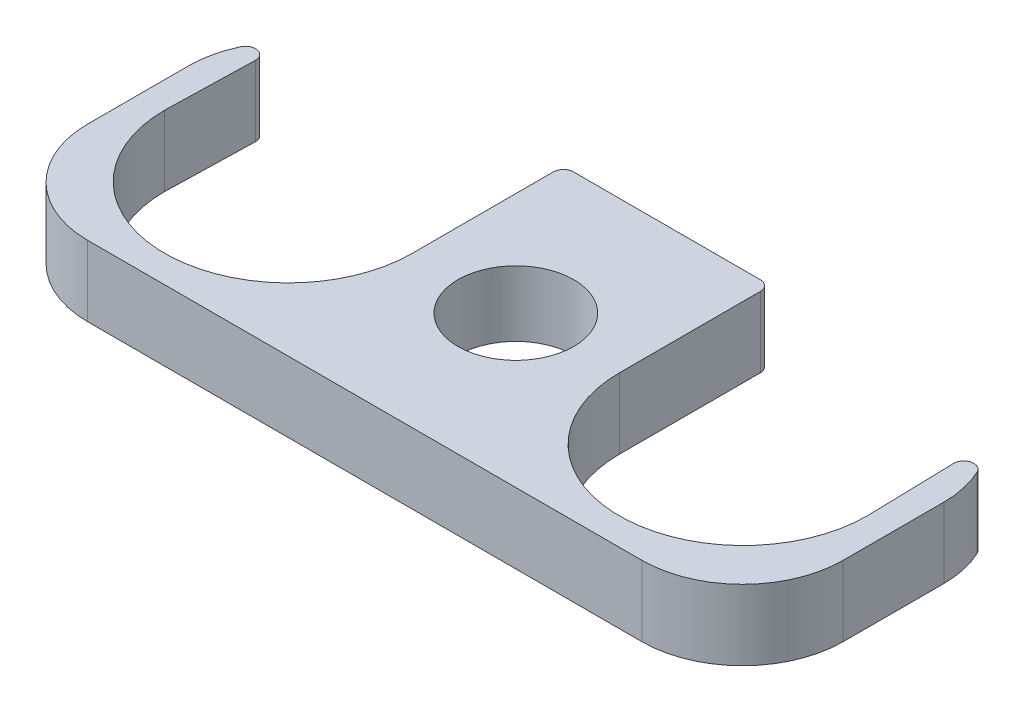
SolidWorks part; units mm, degrees
material "PLA"
ref_plane "Front Plane" through (0, 0, 0) normal (0, 0, 1) x (1, 0, 0)
ref_plane "Top Plane" through (0, 0, 0) normal (0, 1, 0) x (1, 0, 0)
ref_plane "Right Plane" through (0, 0, 0) normal (1, 0, 0) x (0, 0, -1)
sketch "Sketch1" plane through (0, 0, 0) normal (0, 1, 0) x (1, 0, 0)
  line L0 (0, 15) -> (0, -15) construction
  line L1 (-27.5, -15) -> (27.5, -15)
  line L2 (-37.5, -5) -> (-37.5, 5)
  line L3 (-27.5, 15) -> (27.5, 15)
  line L4 (37.5, -5) -> (37.5, 5)
  line L7 (-37.5, 15) -> (0, 15) construction
  line L8 (0, 15) -> (-18.75, 15) construction
  circle A0 centre (0, 0) radius 5.75
  arc A2 (27.5, 15) -> (37.5, 5) centre (27.5, 5) cw
  arc A3 (27.5, -15) -> (37.5, -5) centre (27.5, -5) ccw
  arc A4 (-27.5, -15) -> (-37.5, -5) centre (-27.5, -5) cw
  arc A5 (-37.5, 5) -> (-27.5, 15) centre (-27.5, 5) cw
  point P0 (0, 0)
  point P17 (37.5, -15)
  point P20 (-37.5, -15)
  dimension "D3" = 11.5
  dimension "D5" = 10
  dimension "D1" = 30
  dimension "D2" = 75
extrude "Boss-Extrude1" add sketch "Sketch1" along normal blind 7
sketch "Sketch2" plane through (0, 7, 0) normal (0, 1, 0) x (1, 0, 0)
  line L0 (-34.8757, 0) -> (-34.5711, 12.0711)
  line L1 (-10.2757, 0) -> (-10.2757, 15)
  line L2 (27.5, 15) -> (-27.5, 15) construction
  line L3 (-10.2757, 15) -> (-27.5, 15)
  line L4 (-34.5711, 12.0711) -> (-34.5711, 15)
  line L5 (-34.5711, 15) -> (-27.5, 15)
  circle A0 centre (-22.5757, 0) radius 12.3 construction
  arc A1 (-27.5, 15) -> (-37.5, 5) centre (-27.5, 5) ccw construction
  arc A2 (-34.8757, 0) -> (-10.2757, 0) centre (-22.5757, 0) ccw
  dimension "D1" = 24.6
extrude "Cut-Extrude1" cut sketch "Sketch2" against normal blind 7
fillet "Fillet1" radius 1 1 edges at (-34.5711, 3.5, -12.0711) type face fillet first side face at (8.6122, 3.5, -15) first side face at (-10.2757, 3.5, -7.5) first side face at (-34.7234, 3.5, -6.0355) second side face at (-36.3872, 3.5, -8.6812)
fillet "Fillet2" radius 1 1 edges at (-10.2757, 3.5, -15) type face fillet first side face at (-10.2757, 3.5, -7.5) second side face at (8.6122, 3.5, -15)
ref_axis "Axis1" through (0, 0, 0) along (0, 1, 0)
ref_plane "Plane1" through (0, 0, 0) normal (-1, 0, 0) x (0, 1, 0)
mirror "Mirror1" about plane through (0, 0, 0) normal (-1, 0, 0) of "Cut-Extrude1"
fillet "Fillet3" radius 1 1 edges at (10.2757, 3.5, -15) type face fillet first side face at (0.5, 3.5, -15) second side face at (10.2757, 3.5, -7.5)
fillet "Fillet4" radius 1 1 edges at (34.5711, 3.5, -12.0711) type face fillet first side face at (34.7234, 3.5, -6.0355) second side face at (36.3872, 3.5, -8.6812)
sketch "Sketch3" plane through (0, 0, 0) normal (0, -1, 0) x (1, 0, 0)
  line L0 (0, -8.75) -> (0, 8.75) construction
  line L1 (0, 10.2032) -> (0, -10.2032) construction
  line L3 (0, 10.2016) -> (-8.8349, 5.1008)
  line L4 (-8.8349, 5.1008) -> (-8.8349, -5.1008)
  line L5 (-8.8349, -5.1008) -> (0, -10.2016)
  line L6 (0, -10.2016) -> (8.8349, -5.1008)
  line L7 (8.8349, -5.1008) -> (8.8349, 5.1008)
  line L8 (8.8349, 5.1008) -> (0, 10.2016)
  circle A0 centre (0, 0) radius 8.8349 construction
  dimension "D1" = 17.5
extrude "Cut-Extrude2" cut sketch "Sketch3" against normal blind 0.5
